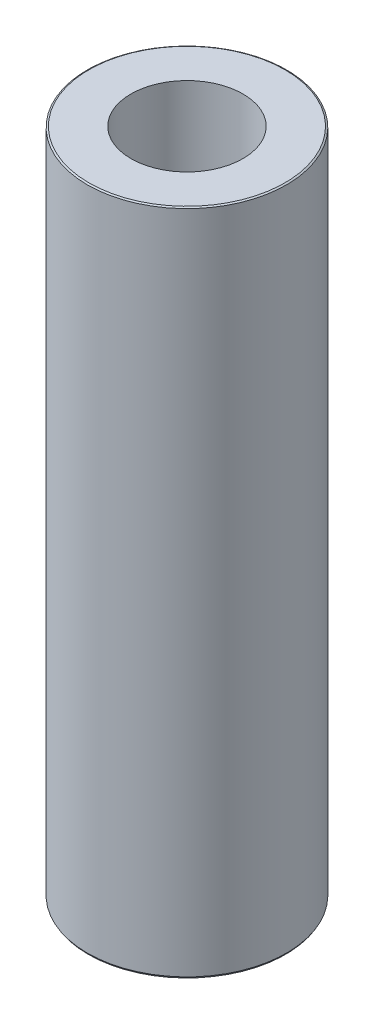
SolidWorks part; units mm, degrees
ref_plane "Front Plane" through (0, 0, 0) normal (0, 0, 1) x (1, 0, 0)
ref_plane "Top Plane" through (0, 0, 0) normal (0, 1, 0) x (1, 0, 0)
ref_plane "Right Plane" through (0, 0, 0) normal (1, 0, 0) x (0, 0, -1)
sketch "Sketch1" plane through (0, 0, 0) normal (0, 1, 0) x (1, 0, 0)
  circle A0 centre (0, 0) radius 55
  dimension "SHAFT_OD" = 110
extrude "Boss-Extrude1" add sketch "Sketch1" along normal blind 368.7897
sketch "Sketch2" plane through (0, 0, 0) normal (0, 1, 0) x (1, 0, 0)
  circle A0 centre (0, 0) radius 30.9465
  dimension "BORE_D" = 61.893
extrude "Cut-Extrude1" cut sketch "Sketch2" along normal through all
chamfer "Chamfer1" distance 0.4994 angle 60.445 2 edges at (0, 368.7897, 55) (0, 0, 55) first distance on face at (0, 368.7897, 55) first distance on face at (0, 0, 30.9465)
